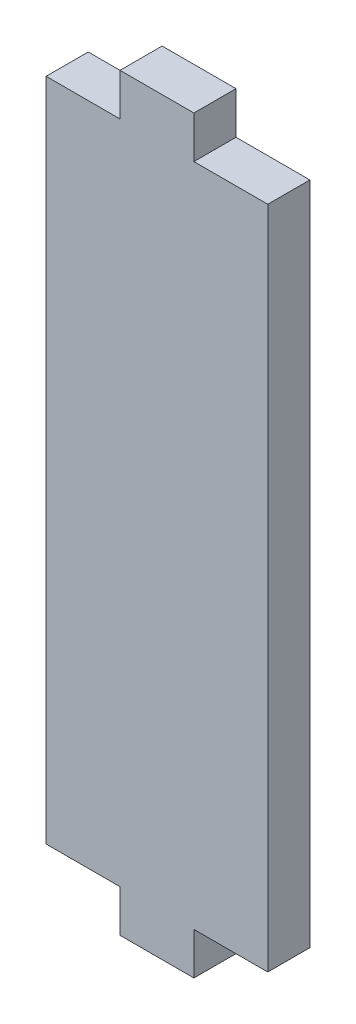
SolidWorks part; units mm, degrees
ref_plane "Front Plane" through (0, 0, 0) normal (0, 0, 1) x (1, 0, 0)
ref_plane "Top Plane" through (0, 0, 0) normal (0, 1, 0) x (1, 0, 0)
ref_plane "Right Plane" through (0, 0, 0) normal (1, 0, 0) x (0, 0, -1)
sketch "Sketch1" plane through (0, 0, 0) normal (0, 0, 1) x (1, 0, 0)
  line L1 (0, 0) -> (25.4, 0)
  line L2 (0, 0) -> (0, 85.852)
  line L3 (0, 85.852) -> (25.4, 85.852)
  line L4 (25.4, 0) -> (25.4, 85.852)
  dimension "D1" = 85.852
  dimension "D2" = 25.4
extrude "Boss-Extrude1" add sketch "Sketch1" along normal blind 4.826
sketch "Sketch2" plane through (0, 0, 4.826) normal (0, 0, 1) x (1, 0, 0)
  line L0 (0, 0) -> (25.4, 0) construction
  line L1 (0, 0) -> (8.4667, 0)
  line L2 (0, 0) -> (0, 4.826)
  line L3 (0, 4.826) -> (8.4667, 4.826)
  line L4 (8.4667, 0) -> (8.4667, 4.826)
  line L5 (8.4667, 4.826) -> (16.9333, 4.826) construction
  line L6 (0, 42.926) -> (25.4, 42.926) construction
  line L7 (0, 85.852) -> (0, 0) construction
  line L8 (8.4667, 81.026) -> (16.9333, 81.026) construction
  line L9 (25.4, 0) -> (25.4, 85.852) construction
  line L10 (16.9333, 0) -> (25.4, 0)
  line L11 (16.9333, 0) -> (16.9333, 4.826)
  line L12 (16.9333, 4.826) -> (25.4, 4.826)
  line L13 (25.4, 0) -> (25.4, 4.826)
  line L14 (25.4, 85.852) -> (25.4, 81.026)
  line L15 (16.9333, 81.026) -> (25.4, 81.026)
  line L16 (16.9333, 85.852) -> (16.9333, 81.026)
  line L17 (16.9333, 85.852) -> (25.4, 85.852)
  line L18 (8.4667, 85.852) -> (8.4667, 81.026)
  line L19 (0, 81.026) -> (8.4667, 81.026)
  line L20 (0, 85.852) -> (0, 81.026)
  line L21 (0, 85.852) -> (8.4667, 85.852)
  dimension "D1" = 4.826
extrude "Cut-Extrude1" cut sketch "Sketch2" against normal through all
equation "\"MDF\"= 0.19in"
equation "\"PVCID\" = 2.067in"
equation "\"PVCOD\" = 2.375in"
equation "\"GenDiameter\"= 60mm"
equation "\"GenCutDiameter\" = 1.8in"
equation "\"GenCutDistance\" = 1"
equation "\"TowerHeight\" = 6in"
equation "\"TowerFrontBase\" = 3in"
equation "\"FunnelHeight\" = 1in"
equation "\"FunnelAngle\" = 20"
equation "\"TowerSideBase\" = 3in"
equation "\"TowerPanelLength\" = 2in"
equation "\"TowerPanelLeeway\" = 0.5in"
equation "\"BaseLength\" = 9in"
equation "\"BaseWidth\" = 10in"
equation "\"WheelHoleLength\" = 3.25in"
equation "\"WheelHoleWidth\" = 26mm"
equation "\"WheelHoleFromBack\" = 1.5in"
equation "\"DropLength\" = 1in"
equation "\"DropWidth\" = 8.5in"
equation "\"BumperWidth\" = 2in"
equation "\"SmallHexDiameter\" = 0.185in"
equation "\"SmallHexHeight\" = 0.701in"
equation "\"ScrewSize\" = 0.106in"
equation "\"BigHexDiameter\" = 0.251in"
equation "\"BigHexHeight\" = 0.374in"
equation "\"PCBThickness\" = 0.066in"
equation "\"ConnectorHeight\" = 0.517in"
equation "\"BoardHeight\" = 0.583in"
equation "\"UnoStackHeight\" = 1.351in"
equation "\"UnoStackWidth\" = 3.053in"
equation "\"UnoStackLength\" = 3.152in"
equation "\"HBridgeWidth\" = 1.797in"
equation "\"HBridgeLength\" = 2.236in"
equation "\"DSWidth\" = 1.820in"
equation "\"DSLength\" = 1.833in"
equation "\"StepperWidth\" = 1.799in"
equation "\"StepperLength\" = 2.248in"
equation "\"ULNWidth\" = 1.304in"
equation "\"ULNLength\" = 1.545in"
equation "\"VSwitchHeight\" = 0.392in"
equation "\"VSwitchWidth\" = 0.637in"
equation "\"VSwitchLength\" = 1.097in"
equation "\"SkateWheelDiameter\" = 80mm"
equation "\"SkateWheelThickness\" = 24mm"
equation "\"BaseDistance\" = 3in"
equation "\"DummyVar\" = 2in"
equation "\"D1@Sketch1\"=2*\"MDF\"+3in"
equation "\"D1@Boss-Extrude1\"=\"MDF\""
equation "\"D1@Sketch2\"=\"MDF\""
